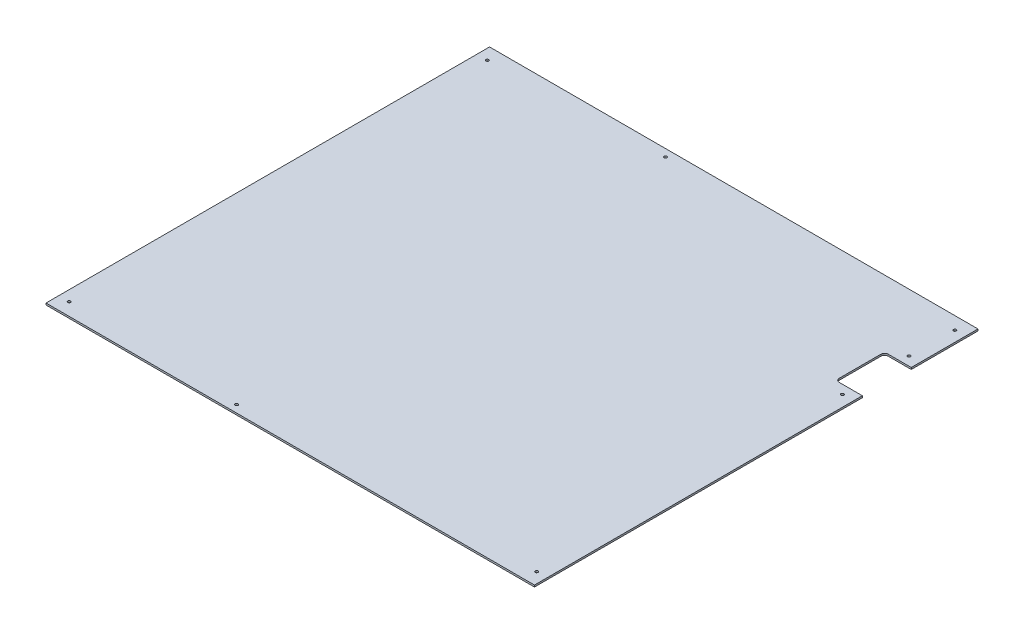
SolidWorks part; units mm, degrees
ref_plane "Alzado" through (0, 0, 0) normal (0, 0, 1) x (1, 0, 0)
ref_plane "Planta" through (0, 0, 0) normal (0, 1, 0) x (1, 0, 0)
ref_plane "Vista lateral" through (0, 0, 0) normal (1, 0, 0) x (0, 0, -1)
sketch "Croquis1" plane through (0, 0, 0) normal (0, 1, 0) x (1, 0, 0)
  line L1 (0, 0) -> (550.5, 0)
  line L2 (0, 0) -> (0, 500)
  line L3 (0, 500) -> (550.5, 500)
  line L4 (550.5, 0) -> (550.5, 500)
  dimension "D1" = 500
  dimension "D2" = 550.5
extrude "Saliente-Extruir1" add sketch "Croquis1" along normal blind 2
sketch "Croquis2" plane through (0, 2, 0) normal (0, 1, 0) x (1, 0, 0)
  line L0 (550.5, 500) -> (0, 500) construction
  line L1 (0, 500) -> (0, 0) construction
  line L2 (275.25, 500) -> (275.25, 0) construction
  line L3 (0, 0) -> (550.5, 0) construction
  line L4 (0, 250) -> (550.5, 250) construction
  line L5 (550.5, 0) -> (550.5, 500) construction
  circle A0 centre (12.5, 485) radius 1.55
  circle A1 centre (538, 485) radius 1.55
  circle A2 centre (538, 15) radius 1.55
  circle A3 centre (12.5, 15) radius 1.55
  dimension "D1" = 3.1
  dimension "D2" = 15
  dimension "D3" = 12.5
extrude "Cortar-Extruir1" cut sketch "Croquis2" against normal up to surface (2 mm away) up to face at (275.25, 0, -250)
sketch "Croquis3" plane through (0, 2, 0) normal (0, 1, 0) x (1, 0, 0)
  line L0 (549.75, 499.25) -> (0.75, 499.25)
  line L1 (0.75, 499.25) -> (0.75, 0.75)
  line L2 (0.75, 0.75) -> (549.75, 0.75)
  line L3 (549.75, 0.75) -> (549.75, 499.25)
  line L4 (0, 500) -> (0, 0)
  line L5 (0, 0) -> (550.5, 0)
  line L6 (550.5, 0) -> (550.5, 500)
  line L7 (550.5, 500) -> (0, 500)
  line L8 (0, 500) -> (0, 0)
  line L9 (0, 0) -> (550.5, 0)
  line L10 (550.5, 0) -> (550.5, 500)
  line L11 (550.5, 500) -> (0, 500)
  dimension "D1" = 0
  dimension "D2" = 0.75
extrude "Cortar-Extruir2" cut sketch "Croquis3" against normal up to surface (2 mm away) up to face at (12.5, 0, -16.55)
sketch "Croquis4" plane through (0, 2, 0) normal (0, 1, 0) x (1, 0, 0)
  line L0 (549.75, 0.75) -> (549.75, 499.25) construction
  line L1 (549.75, 424.25) -> (519.75, 424.25)
  line L2 (549.75, 424.25) -> (549.75, 369.25)
  line L3 (549.75, 369.25) -> (519.75, 369.25)
  line L4 (519.75, 424.25) -> (519.75, 369.25)
  line L5 (549.75, 499.25) -> (0.75, 499.25) construction
  dimension "D1" = 30
  dimension "D2" = 55
  dimension "D3" = 75
extrude "Cortar-Extruir3" cut sketch "Croquis4" against normal up to surface (2 mm away) up to face at (12.5, 0, -486.55)
fillet "Redondeo1" radius 4 2 edges at (519.75, 1, -369.25) (519.75, 1, -424.25)
sketch "Croquis5" plane through (0, 2, 0) normal (0, 1, 0) x (1, 0, 0)
  line L0 (549.75, 424.25) -> (523.75, 424.25) construction
  line L1 (549.75, 424.25) -> (549.75, 499.25) construction
  line L2 (523.75, 369.25) -> (549.75, 369.25) construction
  line L3 (549.75, 0.75) -> (549.75, 369.25) construction
  circle A0 centre (537.25, 434.25) radius 1.6
  circle A1 centre (537.25, 359.25) radius 1.6
  dimension "D1" = 3.2
  dimension "D2" = 10
  dimension "D3" = 12.5
  dimension "D4" = 10
  dimension "D5" = 12.5
extrude "Cortar-Extruir4" cut sketch "Croquis5" against normal up to surface (2 mm away) up to face at (428.5843, 0, -338.05)
sketch "Croquis6" plane through (0, 2, 0) normal (0, 1, 0) x (1, 0, 0)
  line L0 (549.75, 499.25) -> (0.75, 499.25) construction
  line L1 (0.75, 499.25) -> (0.75, 0.75) construction
  line L2 (0.75, 0.75) -> (549.75, 0.75) construction
  circle A0 centre (206.75, 491) radius 1.6
  circle A1 centre (206.75, 9) radius 1.6
  dimension "D1" = 3.2
  dimension "D4" = 3.2
  dimension "D2" = 8.25
  dimension "D3" = 206
  dimension "D5" = 8.25
  dimension "D6" = 206
extrude "Cortar-Extruir5" cut sketch "Croquis6" against normal up to surface (2 mm away) up to face at (537.25, 0, -435.85)
